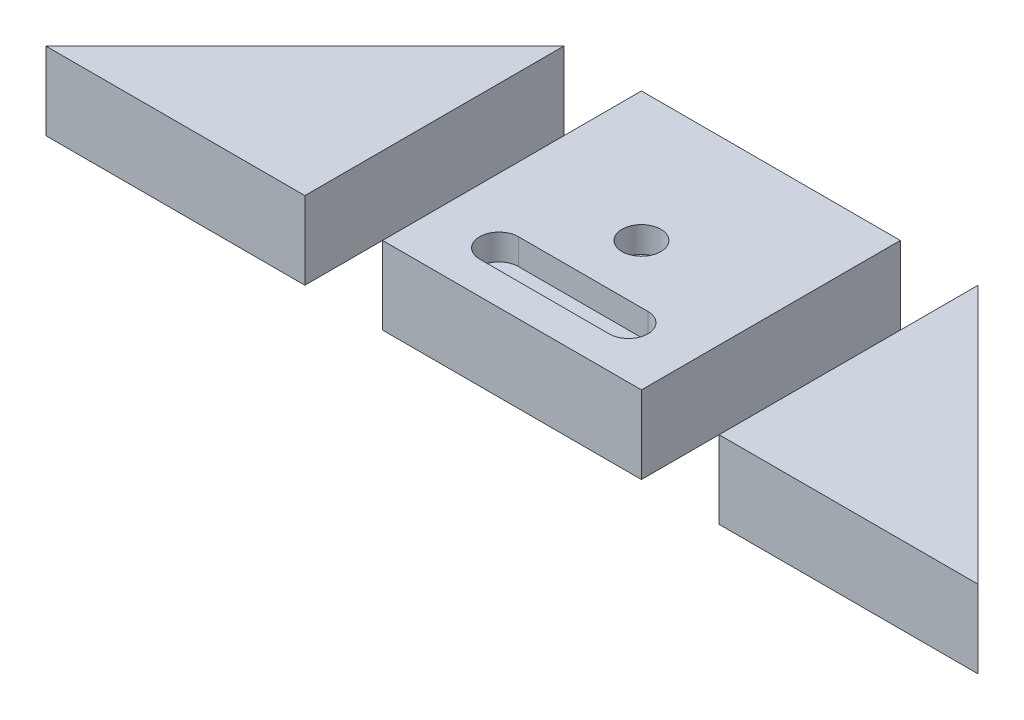
SolidWorks part; units mm, degrees
ref_plane "前视基准面" through (0, 0, 0) normal (0, 0, 1) x (1, 0, 0)
ref_plane "上视基准面" through (0, 0, 0) normal (0, 1, 0) x (1, 0, 0)
ref_plane "右视基准面" through (0, 0, 0) normal (1, 0, 0) x (0, 0, -1)
other "Configuration Table"
sketch "草图1" plane through (0, 0, 0) normal (0, 1, 0) x (1, 0, 0)
  line L0 (80, -50) -> (180, -50)
  line L1 (-50, -50) -> (50, -50)
  line L2 (-50, -50) -> (-50, 50)
  line L3 (-50, 50) -> (50, 50)
  line L4 (50, -50) -> (50, 50)
  line L5 (-50, -50) -> (50, 50) construction
  line L6 (-50, 50) -> (50, -50) construction
  line L7 (180, -50) -> (80, 50)
  line L8 (80, 50) -> (80, -50)
  point P0 (0, 0)
  dimension "D1" = 100
  dimension "D2" = 30
  dimension "D3" = 100
extrude "凸台-拉伸1" add sketch "草图1" along normal blind 30
ref_axis "基准轴1" through (0, 0, 0) along (0, 1, 0)
mirror "镜向1" about plane through (0, 0, 0) normal (1, 0, 0) of bodies 107
sketch "草图2" plane through (0, 30, 0) normal (0, 1, 0) x (1, 0, 0)
  line L0 (-25, -30) -> (25, -30) construction
  line L1 (-25, -22.5) -> (25, -22.5)
  line L2 (-25, -37.5) -> (25, -37.5)
  line L3 (0, 0) -> (0, -30) construction
  circle A0 centre (0, 0) radius 7.5
  arc A1 (-25, -22.5) -> (-25, -37.5) centre (-25, -30) ccw
  arc A2 (25, -37.5) -> (25, -22.5) centre (25, -30) ccw
  point P5 (0, -30)
  dimension "D1" = 15
  dimension "D2" = 15
  dimension "D3" = 50
  dimension "D4" = 30
extrude "切除-拉伸1" cut sketch "草图2" against normal blind 10 contours A0 | L2 A2 L1 A1
